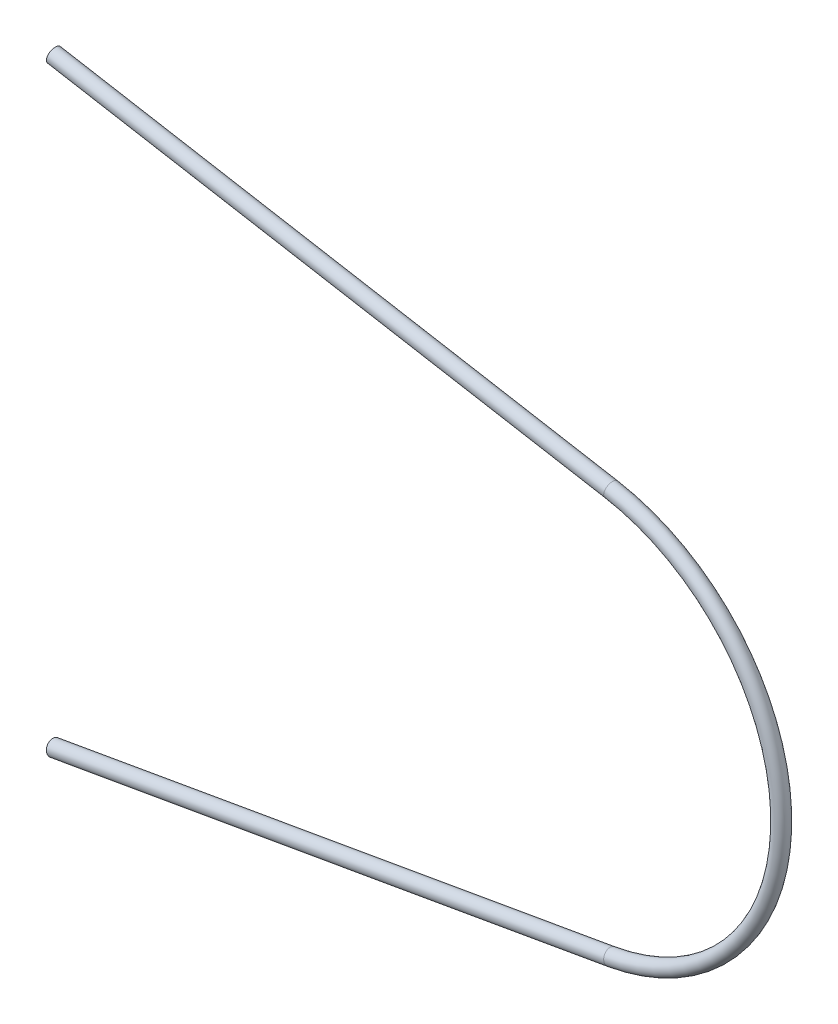
SolidWorks part; units mm, degrees
ref_plane "Front Plane" through (0, 0, 0) normal (0, 0, 1) x (1, 0, 0)
ref_plane "Top Plane" through (0, 0, 0) normal (0, 1, 0) x (1, 0, 0)
ref_plane "Right Plane" through (0, 0, 0) normal (1, 0, 0) x (0, 0, -1)
sketch "Sketch1" plane through (0, 0, 0) normal (0, 1, 0) x (1, 0, 0)
  line L0 (0, 33.9382) -> (0, -33.9382) construction
  point P4 (0, 0)
sketch "Sketch4" [suppressed] plane through (0, 0, 0) normal (0, 1, 0) x (0, 0, -1)
  line L0 (0, -34) -> (6.035, -34)
  line L4 (-6.035, -34) -> (0, -34)
  line L8 (6.035, -34) -> (9.4991, -40)
  line L9 (9.4991, -40) -> (-9.4991, -40)
  line L10 (-9.4991, -40) -> (-6.035, -34)
  dimension "D3" = 12.07
  dimension "D5" = 60
  dimension "D6" = 60
  dimension "D7" = 6
sketch "Sketch2" plane through (0, 0, 0) normal (0, 0, 1) x (1, 0, 0)
  line L2 (6.8966, -39.401) -> (-105.6552, -59.1015)
  line L3 (-105.6552, 59.1015) -> (6.8966, 39.401)
  arc A0 (6.8966, 39.401) -> (6.8966, -39.401) centre (0, 0) cw
  arc A1 (-105.6552, -59.1015) -> (-105.6552, 59.1015) centre (-116, 0) cw construction
  dimension "D1" = 40
  dimension "D2" = 60
  dimension "D3" = 116
sweep "VBeltSweep" [suppressed] add profiles "Sketch4" path "Sketch2"
sketch "Sketch12" plane through (0, 0, 0) normal (0, 1, 0) x (0, 0, -1)
  circle A0 centre (0, -41.5) radius 1.5
  dimension "D1" = 3
  dimension "D2" = 40
sweep "RoundBeltSweep" add profiles "Sketch12" path "Sketch2<2>"
sketch "Sketch2<2>" plane through (0, 0, 0) normal (0, 0, 1) x (1, 0, 0) same geometry as "Sketch2"
